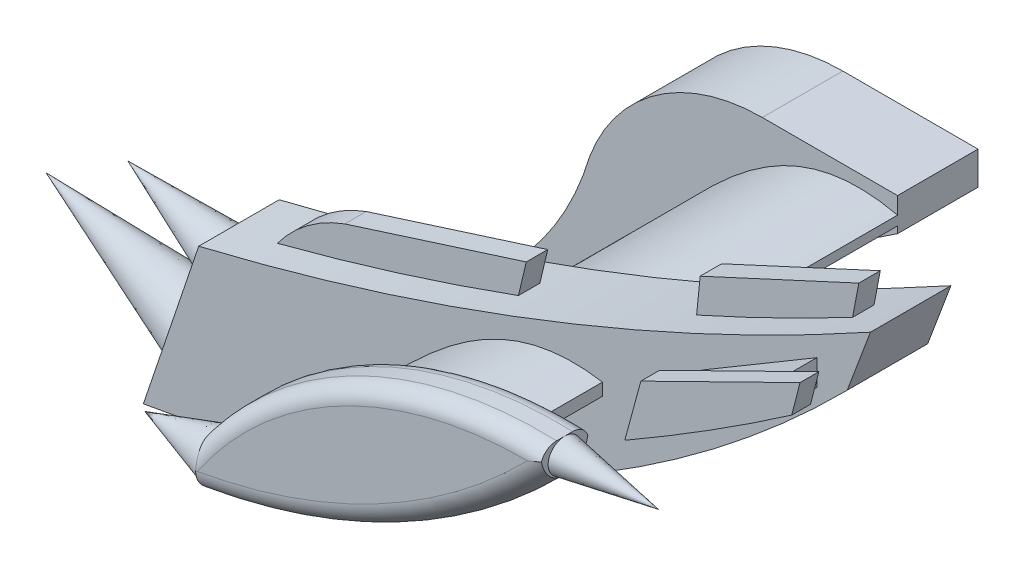
SolidWorks part; units mm, degrees
ref_plane "Front Plane" through (0, 0, 0) normal (0, 0, 1) x (1, 0, 0)
ref_plane "Top Plane" through (0, 0, 0) normal (0, 1, 0) x (1, 0, 0)
ref_plane "Right Plane" through (0, 0, 0) normal (1, 0, 0) x (0, 0, -1)
sketch "Sketch2" plane through (0, 0, 0) normal (0, 0, 1) x (1, 0, 0)
  line L0 (81.7671, 94.989) -> (145.789, 94.989)
  line L1 (145.789, 94.989) -> (145.789, 79.3374)
  arc A0 (0, 38.1) -> (81.7671, 94.989) centre (81.885, 7.6128) cw
  arc A1 (145.789, 79.3374) -> (51.1479, -20.7027) centre (291.2816, -153.09) ccw
  arc A2 (51.1479, -20.7027) -> (-42.2753, -29.0534) centre (-3.9397, 68.8287) cw
  arc A3 (-42.2753, -29.0534) -> (0, 38.1) centre (-141.4625, 80.2718) ccw
  point P0 (0, 38.1)
  point P12 (-42.2753, -29.0534)
  point P13 (51.1479, -20.7027)
  dimension "D1" = 38.1
extrude "Boss-Extrude1" add sketch "Sketch2" along normal blind 38.1
sketch "Sketch3" plane through (0, 0, 38.1) normal (0, 0, 1) x (1, 0, 0)
  line L0 (145.789, 79.3374) -> (145.789, 94.989) construction
  line L1 (145.789, 86.9681) -> (145.789, 82.5464)
  arc A0 (12.8617, 9.0249) -> (47.5274, 13.7759) centre (28.198, 25.9679) ccw
  arc A1 (47.5274, 13.7759) -> (145.789, 82.5464) centre (183.0092, -75.2203) cw
  spline S0 degree 3 poles (145.789, 86.9681) (25.1756, 114.6535) (9.2366, -137.08) (-112.8561, 82.5464) knots 0 0 0 0 1 1 1 1
  point P7 (88.2683, 78.4018)
  point P13 (41.3835, 37.9532)
  line M4 (145.789, 79.3374) -> (145.789, 94.989)
extrude "Boss-Extrude2" add sketch "Sketch3" along normal blind 101.6 contours S0 A0 A1 M4 region at (72.5849, 50.0849, 38.1)
sketch "Sketch4" plane through (0, 0, 139.7) normal (0, 0, 1) x (1, 0, 0)
  line L0 (-45.3861, 48.4845) -> (-71.6098, -29.2707)
  line L1 (272.6642, 172.2546) -> (261.6502, 142.9294)
  arc A0 (-45.3861, 48.4845) -> (272.6642, 172.2546) centre (-344.1877, 1286.8405) ccw
  arc A1 (-71.6098, -29.2707) -> (261.6502, 142.9294) centre (-169.9455, 569.6192) ccw
  point P4 (229.1996, 149.2839)
  point P5 (214.1415, 78.1384)
  point P8 (-45.3861, 48.4845)
  point P9 (261.6502, 142.9294)
extrude "Boss-Extrude3" add sketch "Sketch4" along normal blind 38.1
sketch "Sketch7" plane through (0, 0, 177.8) normal (0, 0, 1) x (1, 0, 0)
  line L0 (145.789, 86.9681) -> (145.789, 82.5464) construction
  line L1 (145.789, 88.35) -> (145.789, 82.5464)
  arc A0 (12.8617, 9.0249) -> (47.5274, 13.7759) centre (28.198, 25.9679) ccw
  arc A1 (47.5274, 13.7759) -> (145.789, 82.5464) centre (183.0092, -75.2203) cw
  arc A2 (12.8617, 9.0249) -> (47.5274, 13.7759) centre (28.198, 25.9679) ccw construction
  arc A3 (145.789, 82.5464) -> (47.5274, 13.7759) centre (183.0092, -75.2203) ccw construction
  spline S0 degree 3 poles (145.789, 88.35) (23.1067, 108.7023) (0.9946, -148.298) (-122.6566, 96.1934) knots 0 0 0 0 1 1 1 1
  spline S3 degree 3 poles (145.789, 86.9681) (25.1756, 114.6535) (9.2366, -137.08) (-112.8561, 82.5464) knots 0 0 0 0 1 1 1 1 construction
  point P7 (-1.0661, 25.677)
  point P10 (33.5996, 30.428)
  point P21 (145.789, 88.35)
extrude "Boss-Extrude4" add sketch "Sketch7" along normal blind 25.4 contours L1 S0 A0 A1 region at (72.9426, 49.7415, 177.8)
sketch "Sketch8" plane through (0, 0, 203.2) normal (0, 0, 1) x (1, 0, 0)
  line L0 (1.4222, 16.0118) -> (1.4222, -6.3891)
  line L1 (164.6974, 94.0507) -> (164.6974, 78.4182)
  arc A0 (1.4222, 16.0118) -> (164.6974, 94.0507) centre (157.7104, -101.1549) cw
  arc A1 (1.4222, -6.3891) -> (164.6974, 78.4182) centre (-47.6772, 287.7158) ccw
  point P6 (1.4222, 16.0118)
  line M5 (145.789, 82.5464) -> (145.789, 88.35)
  spline M6 degree 3 poles (145.789, 88.35) (23.1067, 108.7023) (0.9946, -148.298) (-122.6566, 96.1934) knots 0 0 0 0 1 1 1 1 only from (145.789, 88.35) to (12.8617, 9.0249)
  arc M7 (12.8617, 9.0249) -> (47.5274, 13.7759) centre (28.198, 25.9679) ccw
  arc M8 (47.5274, 13.7759) -> (145.789, 82.5464) centre (183.0092, -75.2203) cw
extrude "Boss-Extrude5" add sketch "Sketch8" along normal blind 22.86 contours L0 A1 L1 A0 M5 M8 M7 M6 | L0 | M8 M5 M6 M7 | L1 region at (80.3441, 47.3409, 203.2)
ref_plane "Plane1" through (0, 0, 158.75) normal (0, 0, 1) x (1, 0, 0)
sketch "Sketch9" plane through (0, 0, 158.75) normal (0, 0, 1) x (1, 0, 0)
  line L0 (-62.3073, -1.6882) -> (-136.7489, 23.4179)
  line L1 (-45.3861, 48.4845) -> (-71.6098, -29.2707) construction
  line L2 (-136.7489, 23.4179) -> (-67.6312, -17.4741)
  line L3 (-67.6312, -17.4741) -> (-62.3073, -1.6882)
  point P4 (-136.7489, 23.4179)
revolve "Revolve1" add sketch "Sketch9" angle 360 about L0
sketch "Sketch10" plane through (0, 0, 158.75) normal (0, 0, 1) x (1, 0, 0)
  line L0 (-50.8488, 32.2871) -> (-54.5914, 21.1901)
  line L1 (-45.3861, 48.4845) -> (-71.6098, -29.2707) construction
  line L2 (-54.5914, 21.1901) -> (-98.023, 47.6171)
  line L3 (-98.023, 47.6171) -> (-50.8488, 32.2871)
  point P4 (-84.6484, 43.0679)
  point P6 (-98.023, 47.6171)
revolve "Revolve2" add sketch "Sketch10" angle 360 about L3
ref_plane "Plane2" through (0, 0, 214.63) normal (0, 0, 1) x (1, 0, 0)
sketch "Sketch11" plane through (0, 0, 214.63) normal (0, 0, 1) x (1, 0, 0)
  line L0 (1.4222, 4.8113) -> (-34.0353, 4.8113)
  line L1 (1.4222, 16.0118) -> (1.4222, -6.3891) construction
  line L2 (-34.0353, 4.8113) -> (1.4222, -6.3891)
  line L3 (1.4222, -6.3891) -> (1.4222, 4.8113)
revolve "Revolve3" add sketch "Sketch11" angle 360 about L0
sketch "Sketch12" plane through (0, 0, 214.63) normal (0, 0, 1) x (1, 0, 0)
  line L0 (164.6974, 86.2344) -> (209.1363, 86.2344)
  line L1 (164.6974, 94.0507) -> (164.6974, 78.4182) construction
  line L2 (164.6974, 78.4182) -> (209.1363, 86.2344)
  line L3 (164.6974, 78.4182) -> (164.6974, 86.2344)
revolve "Revolve4" add sketch "Sketch12" angle 360 about L0
fillet "Fillet5" radius 7.62 1 edges at (73.4772, 75.0802, 226.06)
fillet "Fillet6" radius 7.62 1 edges at (73.4772, 75.0802, 203.2)
fillet "Fillet8" radius 10.16 2 edges at (89.7645, 23.1063, 203.2) (89.7645, 23.1063, 226.06)
sketch "Sketch13" plane through (0, 0, 158.75) normal (0, 0, 1) x (1, 0, 0)
  line L0 (9.8099, 78.2424) -> (95.7358, 105.6114)
  line L1 (95.7358, 105.6114) -> (92.0247, 89.9584)
  line L2 (176.3905, 124.1684) -> (178.0526, 140.9332)
  line L3 (178.0526, 140.9332) -> (253.2016, 175.666)
  line L4 (253.2016, 175.666) -> (250.2253, 160.128)
  arc A0 (-22.0818, 54.3407) -> (9.8099, 78.2424) centre (33.2237, 13.7745) cw
  arc A1 (-45.3861, 48.4845) -> (272.6642, 172.2546) centre (-344.1877, 1286.8405) ccw construction
  arc A2 (-45.3861, 48.4845) -> (272.6642, 172.2546) centre (-344.1877, 1286.8405) ccw
  arc A3 (-22.0818, 54.3407) -> (92.0247, 89.9584) centre (-69.286, 406.1532) ccw
  arc A4 (176.3905, 124.1684) -> (250.2253, 160.128) centre (140.659, 291.3164) ccw
extrude "Boss-Extrude6" add sketch "Sketch13" along normal blind 5.08 and the other way blind 5.08 contours A0 A2 L1 L0 | L2 A2 L4 L3 region at (213.6996, 149.6408, 158.75) region at (40.7201, 80.2683, 158.75)
sketch "Sketch14" plane through (0, 0, 177.8) normal (0, 0, 1) x (1, 0, 0)
  line L0 (192.7474, 116.764) -> (192.7474, 100.3645)
  line L1 (192.7474, 100.3645) -> (247.2587, 136.8593)
  line L2 (247.2587, 136.8593) -> (247.2587, 149.1012)
  line L3 (247.2587, 149.1012) -> (192.7474, 116.764)
extrude "Boss-Extrude7" add sketch "Sketch14" along normal blind 15.24
sketch "Sketch15" plane through (0, 0, 193.04) normal (0, 0, 1) x (1, 0, 0)
  line L0 (180.4793, 93.8992) -> (188.0882, 121.9649)
  line L1 (188.0882, 121.9649) -> (263.4584, 159.0475)
  line L2 (259.5221, 143.7286) -> (263.4584, 159.0475)
  arc A0 (180.4793, 93.8992) -> (259.5221, 143.7286) centre (-396.6489, 1096.9842) ccw
extrude "Boss-Extrude8" add sketch "Sketch15" along normal blind 8.89
sketch3d "3DSketch1"
  spline S0 degree 3 poles (1404.4854, -2621.1189, 177.8) (-710.1049, 3241.9924, 177.8) (661.2262, -3219.4801, 177.8) (-930.7721, 2847.1476, 177.8) knots -2.454622 -2.454622 -2.454622 -2.454622 3.94374 3.94374 3.94374 3.94374 only from (145.789, 88.35, 177.8) to (12.8617, 9.0249, 177.8) construction
  spline S1 degree 3 poles (145.789, 88.35, 177.8) (84.9726, 98.4391, 177.8) (48.8704, 40.3713, 177.8) (12.8617, 9.0249, 177.8) knots 0 0 0 0 1 1 1 1
